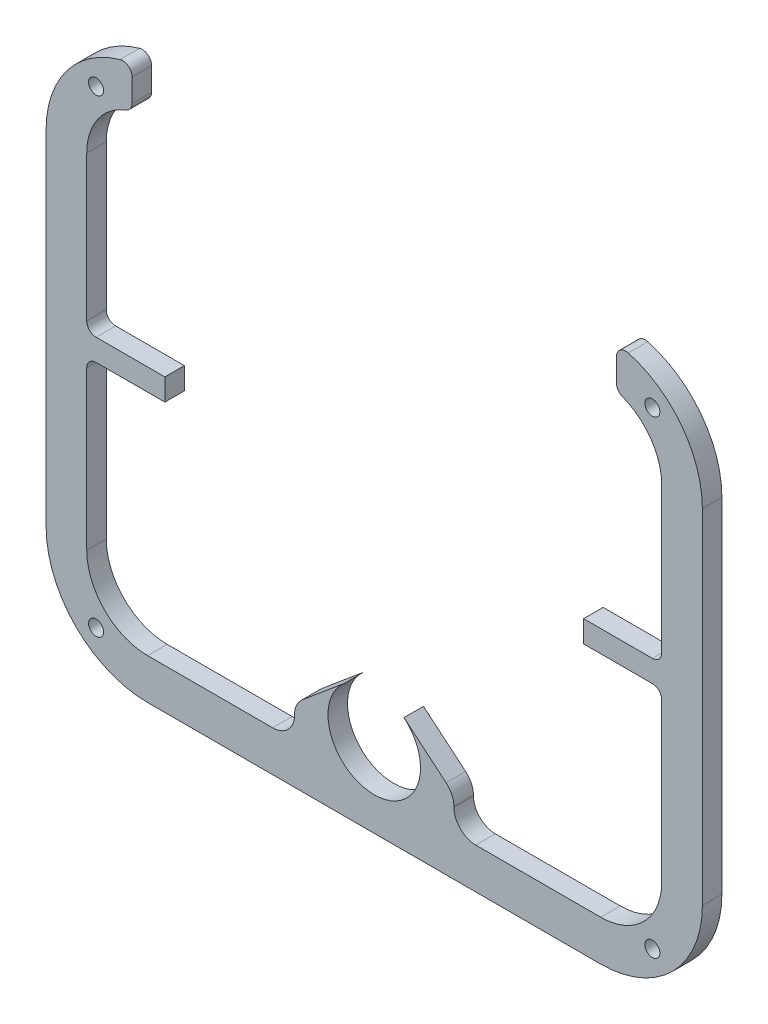
SolidWorks part; units mm, degrees
material "Delrin 2700 NC010, Low Viscosity Acetal Copolymer (SS)"
ref_plane "Front Plane" through (0, 0, 0) normal (0, 0, 1) x (1, 0, 0)
ref_plane "Top Plane" through (0, 0, 0) normal (0, 1, 0) x (1, 0, 0)
ref_plane "Right Plane" through (0, 0, 0) normal (1, 0, 0) x (0, 0, -1)
sketch "Sketch1" plane through (0, 0, 0) normal (0, 0, 1) x (1, 0, 0)
  line L0 (-18.415, -18.923) -> (-9.6321, -18.923)
  line L1 (18.415, 22.225) -> (-18.415, 22.225)
  line L2 (26.67, 13.97) -> (26.67, -13.97)
  line L3 (18.415, -22.225) -> (-18.415, -22.225)
  line L4 (-26.67, 13.97) -> (-26.67, -13.97)
  line L5 (26.67, 22.225) -> (-26.67, -22.225) construction
  line L6 (26.67, -22.225) -> (-26.67, 22.225) construction
  line L7 (9.6321, -18.923) -> (18.415, -18.923)
  line L8 (-23.368, -0.381) -> (-17.018, -0.381)
  line L9 (23.368, 1.397) -> (17.018, 1.397)
  line L10 (-23.368, 13.97) -> (-23.368, -13.97)
  line L11 (-1000, 0) -> (49000, 0) construction
  line L12 (-23.368, 0) -> (-23.368, -1.27)
  line L13 (23.368, 13.97) -> (23.368, -13.97)
  line L14 (18.415, 18.923) -> (-18.415, 18.923)
  line L15 (23.368, 1.397) -> (23.368, -0.381)
  line L16 (23.368, -0.381) -> (17.018, -0.381)
  line L17 (17.018, 1.397) -> (17.018, -0.381)
  line L18 (0, 18.923) -> (0, -18.415) construction
  line L19 (-17.018, 1.397) -> (-17.018, -0.381)
  line L20 (-23.368, 1.397) -> (-17.018, 1.397)
  line L21 (2.4164, -12.8683) -> (9.6321, -18.923)
  line L22 (-2.4164, -12.8683) -> (-9.6321, -18.923)
  line L36 (18.415, -18.923) -> (-18.415, -18.923) construction
  arc A0 (-2.4164, -12.8683) -> (2.4164, -12.8683) centre (0, -15.748) ccw
  arc A1 (-18.415, 22.225) -> (-26.67, 13.97) centre (-18.415, 13.97) ccw
  arc A2 (18.415, 22.225) -> (26.67, 13.97) centre (18.415, 13.97) cw
  arc A3 (26.67, -13.97) -> (18.415, -22.225) centre (18.415, -13.97) cw
  arc A4 (-18.415, -22.225) -> (-26.67, -13.97) centre (-18.415, -13.97) cw
  arc A7 (18.415, 18.923) -> (23.368, 13.97) centre (18.415, 13.97) cw
  arc A8 (-18.415, 18.923) -> (-23.368, 13.97) centre (-18.415, 13.97) ccw
  circle A9 centre (-22.606, 19.05) radius 0.6096
  circle A10 centre (22.606, 19.05) radius 0.6096
  circle A11 centre (-22.606, -19.05) radius 0.6096
  circle A12 centre (22.606, -19.05) radius 0.6096
  arc A13 (-18.415, -18.923) -> (-23.368, -13.97) centre (-18.415, -13.97) cw construction
  arc A14 (23.368, -13.97) -> (18.415, -18.923) centre (18.415, -13.97) cw construction
  arc A15 (-23.368, -13.97) -> (-18.415, -18.923) centre (-18.415, -13.97) ccw
  arc A16 (18.415, -18.923) -> (23.368, -13.97) centre (18.415, -13.97) ccw
  point P0 (0, 0)
  dimension "D4" = 7.5184
  dimension "D6" = 8.255
  dimension "D7" = 8.255
  dimension "D8" = 8.255
  dimension "D9" = 8.255
  dimension "D5" = 1.2192
  dimension "D1" = 53.34
  dimension "D2" = 44.45
  dimension "D10" = 3.302
  dimension "D3" = 3.175
  dimension "D11" = 3.175
  dimension "D12" = 4.064
  dimension "D13" = 15.748
  dimension "D14" = 1.778
  dimension "D15" = 21.844
  dimension "D16" = 6.35
extrude "Boss-Extrude1" add sketch "Sketch1" along normal blind 1.5875 contours A4 L3 A3 L2 A2 L1 A1 L4 A16 L7 L21 A0 L22 L0 A15 L10 A8 L14 A7 L13 A12 A10 A9 A11 | L9 L17 L16 L13 | L20 L10 L8 L19 region at (-20.193, 0.508, 0) region at (20.193, 0.508, 0) region at (23.7612, 19.3162, 0)
sketch "Sketch2" plane through (0, 0, 1.5875) normal (0, 0, 1) x (1, 0, 0)
  line L1 (-9.6321, -18.923) -> (-6.477, -18.923)
  line L2 (-9.6321, -18.923) -> (-9.6321, -16.2756)
  line L3 (-9.6321, -16.2756) -> (-6.477, -16.2756)
  line L4 (-6.477, -18.923) -> (-6.477, -16.2756)
  line L5 (0, -1000) -> (0, 49000) construction
  line L6 (9.6321, -18.923) -> (9.6321, -16.2756)
  line L7 (9.6321, -16.2756) -> (6.477, -16.2756)
  line L8 (6.477, -18.923) -> (6.477, -16.2756)
  line L9 (9.6321, -18.923) -> (6.477, -18.923)
  line L11 (-18.415, 18.923) -> (18.415, 18.923)
  line L12 (-19.685, 18.7574) -> (-19.685, 22.225)
  line L13 (-19.685, 22.225) -> (19.685, 22.225)
  line L14 (19.685, 18.7574) -> (19.685, 22.225)
  line L16 (18.415, 18.923) -> (-18.415, 18.923) construction
  line L17 (-2.4164, -12.8683) -> (-9.6321, -18.923) construction
  line L18 (18.415, 22.225) -> (-18.415, 22.225) construction
  arc A0 (23.368, 13.97) -> (18.415, 18.923) centre (18.415, 13.97) ccw construction
  arc A1 (-18.415, 18.923) -> (-23.368, 13.97) centre (-18.415, 13.97) ccw construction
  arc A2 (19.685, 18.7574) -> (18.415, 18.923) centre (18.415, 13.97) ccw
  arc A3 (-18.415, 18.923) -> (-19.685, 18.7574) centre (-18.415, 13.97) ccw
  point P25 (0, 22.225)
  dimension "D1" = 6.477
  dimension "D2" = 39.37
extrude "Cut-Extrude1" cut sketch "Sketch2" against normal up to next
fillet "Fillet1" radius 1.778 4 edges at (6.477, -18.923, 0.7937) (6.477, -16.2756, 0.7937) (-6.477, -18.923, 0.7937) (-6.477, -16.2756, 0.7937)
fillet "Fillet2" radius 0.762 4 edges at (19.685, 22.1267, 0.7937) (19.685, 18.7574, 0.7937) (-19.685, 18.7574, 0.7937) (-19.685, 22.1267, 0.7937)
fillet "Fillet3" radius 0.762 4 edges at (-23.368, -0.381, 0.7937) (23.368, -0.381, 0.7937) (23.368, 1.397, 0.7937) (-23.368, 1.397, 0.7937)
